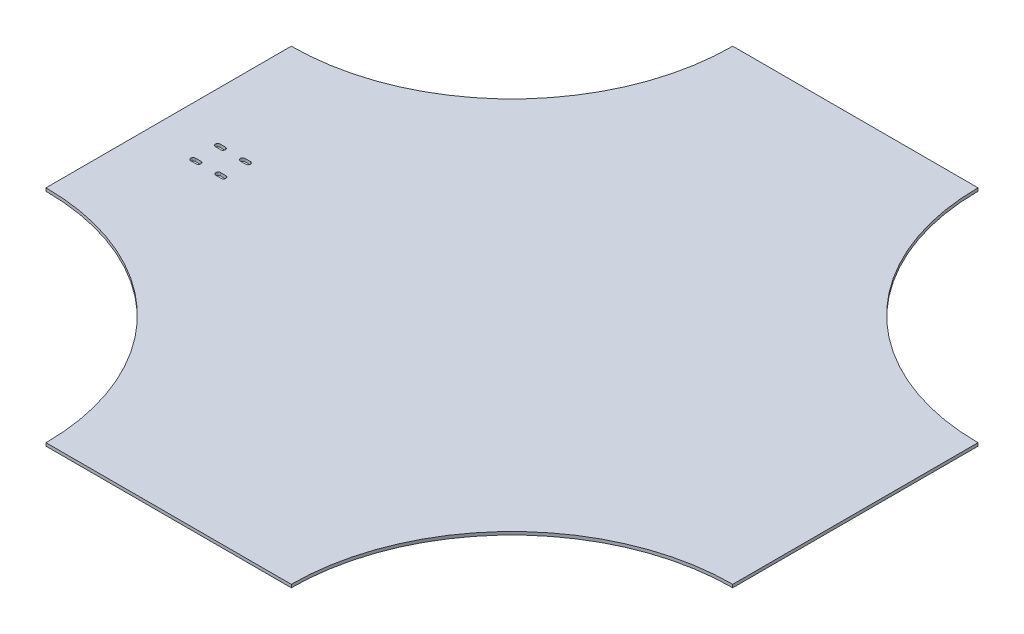
SolidWorks part; units mm, degrees
ref_plane "Front Plane" through (0, 0, 0) normal (0, 0, 1) x (1, 0, 0)
ref_plane "Top Plane" through (0, 0, 0) normal (0, 1, 0) x (1, 0, 0)
ref_plane "Right Plane" through (0, 0, 0) normal (1, 0, 0) x (0, 0, -1)
sketch "Sketch1" plane through (0, 0, 0) normal (0, 1, 0) x (1, 0, 0)
  line L9 (-127, -355.6) -> (127, -355.6)
  line L10 (-355.6, -127) -> (-355.6, 127)
  line L11 (-127, 355.6) -> (127, 355.6)
  line L12 (355.6, -127) -> (355.6, 127)
  line L13 (-193.9554, -193.9554) -> (193.9554, 193.9554) construction
  line L14 (-193.9554, 193.9554) -> (193.9554, -193.9554) construction
  arc A8 (-355.6, 127) -> (-127, 355.6) centre (-355.6, 355.6) ccw
  arc A9 (127, 355.6) -> (355.6, 127) centre (355.6, 355.6) ccw
  arc A10 (355.6, -127) -> (127, -355.6) centre (355.6, -355.6) ccw
  arc A11 (-127, -355.6) -> (-355.6, -127) centre (-355.6, -355.6) ccw
  point P0 (0, 0)
  point P1 (0, 0)
  point P2 (0, 0)
  dimension "D3" = 457.2
  dimension "D4" = 457.2
  dimension "D5" = 457.2
  dimension "D6" = 457.2
  dimension "D1" = 711.2
  dimension "D2" = 711.2
extrude "Boss-Extrude1" add sketch "Sketch1" along normal blind 3.175
sketch "Sketch2" plane through (0, 3.175, 0) normal (0, 1, 0) x (1, 0, 0)
  line L0 (-304.8, 2.413) -> (-299.212, 2.413)
  line L1 (-304.8, -22.987) -> (-299.212, -22.987)
  line L2 (-299.212, -2.413) -> (-304.8, -2.413)
  line L3 (-278.892, -2.413) -> (-273.304, -2.413)
  line L4 (-278.892, -22.987) -> (-273.304, -22.987)
  line L5 (-273.304, 2.413) -> (-278.892, 2.413)
  line L6 (-299.212, -27.813) -> (-304.8, -27.813)
  line L7 (-355.6, 127) -> (-355.6, -127) construction
  line L8 (-273.304, -27.813) -> (-278.892, -27.813)
  arc A0 (-299.212, -2.413) -> (-299.212, 2.413) centre (-299.212, 0) ccw
  arc A1 (-273.304, -2.413) -> (-273.304, 2.413) centre (-273.304, 0) ccw
  arc A2 (-273.304, -27.813) -> (-273.304, -22.987) centre (-273.304, -25.4) ccw
  arc A3 (-299.212, -27.813) -> (-299.212, -22.987) centre (-299.212, -25.4) ccw
  arc A4 (-278.892, 2.413) -> (-278.892, -2.413) centre (-278.892, 0) ccw
  arc A5 (-304.8, 2.413) -> (-304.8, -2.413) centre (-304.8, 0) ccw
  arc A6 (-304.8, -22.987) -> (-304.8, -27.813) centre (-304.8, -25.4) ccw
  arc A7 (-278.892, -22.987) -> (-278.892, -27.813) centre (-278.892, -25.4) ccw
  dimension "D1" = 4.826
  dimension "D2" = 4.826
  dimension "D3" = 4.826
  dimension "D4" = 4.826
  dimension "D5" = 4.826
  dimension "D6" = 4.826
  dimension "D7" = 4.826
  dimension "D8" = 4.826
  dimension "D9" = 5.588
  dimension "D10" = 5.588
  dimension "D11" = 5.588
  dimension "D12" = 5.588
  dimension "D13" = 20.32
  dimension "D14" = 20.32
  dimension "D15" = 25.4
  dimension "D16" = 25.4
  dimension "D17" = 0
  dimension "D18" = 50.8
extrude "Cut-Extrude1" cut sketch "Sketch2" against normal through all both and the other way through all
